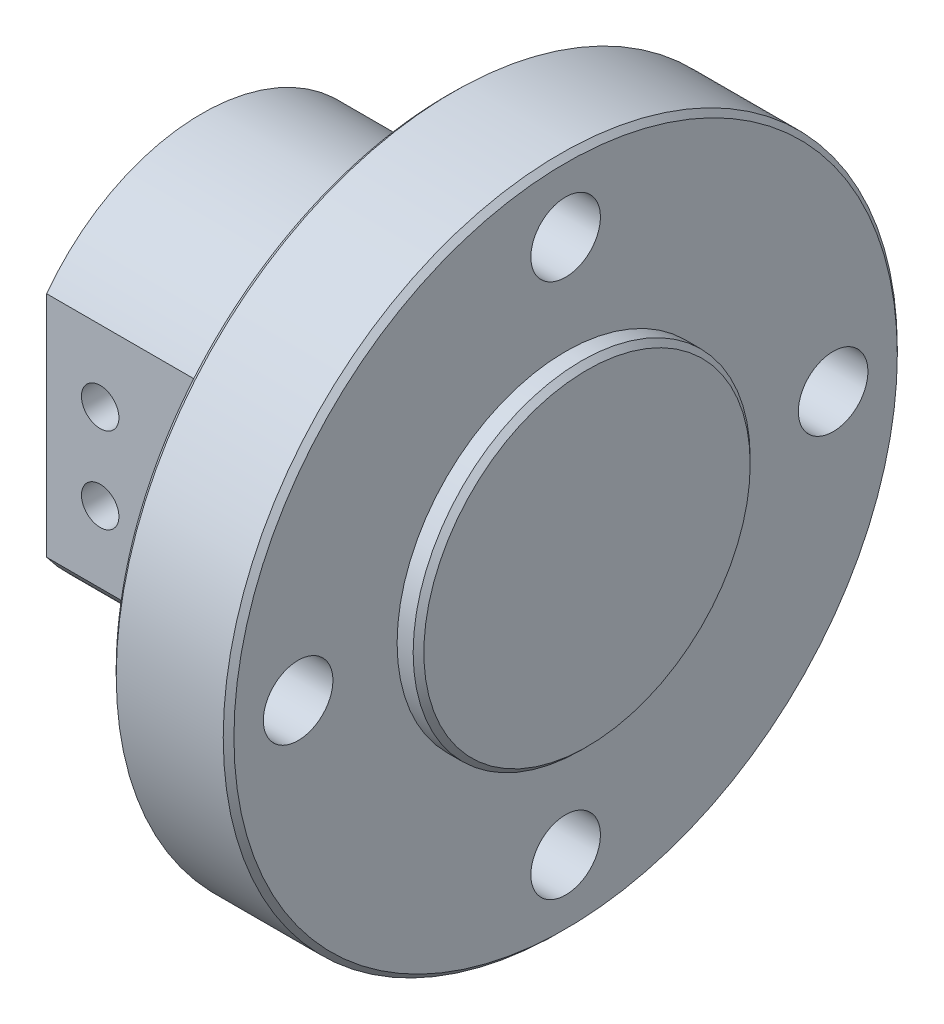
SolidWorks part; units mm, degrees
material "7079 Alloy"
ref_plane "Front Plane" through (0, 0, 0) normal (0, 0, 1) x (1, 0, 0)
ref_plane "Top Plane" through (0, 0, 0) normal (0, 1, 0) x (1, 0, 0)
ref_plane "Right Plane" through (0, 0, 0) normal (1, 0, 0) x (0, 0, -1)
sketch "Sketch1" plane through (0, 0, 0) normal (1, 0, 0) x (0, 0, -1)
  circle A0 centre (0, 0) radius 31.5
  dimension "D1" = 63
extrude "Boss-Extrude1" add sketch "Sketch1" along normal blind 11
sketch "Sketch2" plane through (0, 0, 0) normal (-1, 0, 0) x (0, 0, 1)
  circle A0 centre (0, 0) radius 25 construction
  circle A1 centre (0, 25) radius 3.25
  circle A2 centre (0, -25) radius 3.25
  dimension "D1" = 50
  dimension "D2" = 6.5
extrude "Cut-Extrude1" cut sketch "Sketch2" against normal through all
sketch "Sketch3" plane through (0, 0, 0) normal (-1, 0, 0) x (0, 0, 1)
  circle A0 centre (0, 25) radius 6
  circle A1 centre (0, -25) radius 6
  dimension "D1" = 12
extrude "Cut-Extrude2" cut sketch "Sketch3" against normal blind 5
chamfer "Chamfer1" distance 0.5 angle 45 2 edges at (0, 0, -31.5) (11, 0, -31.5)
sketch "Sketch4" plane through (11, 0, 0) normal (1, 0, 0) x (0, 0, -1)
  circle A0 centre (0, 0) radius 15.75
  dimension "D1" = 31.5
extrude "Boss-Extrude2" add sketch "Sketch4" along normal blind 2
chamfer "Chamfer2" distance 0.5 angle 45 1 edges at (13, 0, -15.75)
sketch "Sketch5" plane through (0, 0, 0) normal (-1, 0, 0) x (0, 0, 1)
  circle A0 centre (0, 0) radius 10.5
  circle A1 centre (0, 0) radius 18
  dimension "D1" = 21
  dimension "D2" = 36
extrude "Boss-Extrude3" add sketch "Sketch5" along normal blind 23
sketch "Sketch6" plane through (-23, 0, 0) normal (-1, 0, 0) x (0, 0, 1)
  line L1 (-8.5, 6.1644) -> (8.5, 6.1644)
  line L2 (-8.5, 6.1644) -> (-8.5, -6.1644)
  line L3 (-8.5, -6.1644) -> (8.5, -6.1644)
  line L4 (8.5, 6.1644) -> (8.5, -6.1644)
  circle A0 centre (0, 0) radius 10.5 construction
  circle A1 centre (0, 0) radius 10.5
  circle M7 centre (0, 0) radius 10.5
  dimension "D1" = 8.5
  dimension "D2" = 12.3288
extrude "Boss-Extrude4" add sketch "Sketch6" against normal up to next contours L4 M7 | L2 M7 region at (-23, 0, -9.3069) region at (-23, 0, 9.3069)
sketch "Sketch7" plane through (-23, 0, 0) normal (-1, 0, 0) x (0, 0, 1)
  line L0 (8.5, 6.1644) -> (8.5, -6.1644) construction
  line L1 (-14.5, 10.6654) -> (14.5, 10.6654)
  line L2 (-14.5, 10.6654) -> (-14.5, -10.6654)
  line L3 (-14.5, -10.6654) -> (14.5, -10.6654)
  line L4 (14.5, 10.6654) -> (14.5, -10.6654)
  circle A1 centre (0, 0) radius 18
  circle A2 centre (0, 0) radius 18
  circle M6 centre (0, 0) radius 18
  dimension "D2" = 6
  dimension "D1" = 0
extrude "Cut-Extrude3" cut sketch "Sketch7" against normal blind 22 contours L4 M6 | L2 M6 region at (-23, 0, -15.9124) region at (-23, 0, 15.9124)
sketch "Sketch8" plane through (0, 0, 14.5) normal (0, 0, 1) x (1, 0, 0)
  line L0 (-23, 10.6654) -> (-23, -10.6654) construction
  line L1 (-18, 4) -> (-6, 4) construction
  line L2 (-18, 4) -> (-18, -4)
  line L3 (-18, -4) -> (-6, -4) construction
  line L4 (-6, 4) -> (-6, -4)
  line L5 (-6, 0) -> (0, 0) construction
  circle A0 centre (-18, 4) radius 1.75
  circle A1 centre (-6, 4) radius 1.75
  circle A2 centre (-6, -4) radius 1.75
  circle A3 centre (-18, -4) radius 1.75
  dimension "D4" = 3.5
  dimension "D1" = 5
  dimension "D2" = 12
  dimension "D3" = 8
extrude "Cut-Extrude4" cut sketch "Sketch8" against normal through all contours A0 | A1 | A2 | A3 region at (-16.7976, -2.7976, 14.5) region at (-19.2024, 5.2024, 14.5) region at (-4.7976, -2.7976, 14.5) region at (-7.2024, 5.2024, 14.5)
pattern_circular "CirPattern1" count 4 over 360 about axis through (11, 0, 0) along (-1, 0, 0) of "Cut-Extrude2", "Cut-Extrude1" reverse direction yes
sketch "Sketch9" plane through (-23, 0, 0) normal (-1, 0, 0) x (0, 0, 1)
  line L0 (-8.5, 6.1644) -> (-8.5, -6.1644) construction
  line L1 (8.5, 6.1644) -> (8.5, -6.1644) construction
  line L2 (-8.5, 6.1644) -> (-8.5, -6.1644)
  line L3 (8.5, 6.1644) -> (8.5, -6.1644)
  line L4 (-8.6, 6.1968) -> (-8.6, -6.1968)
  line L5 (8.6, 6.1968) -> (8.6, -6.1968)
  arc A0 (-8.5, -6.1644) -> (8.5, -6.1644) centre (0, 0) ccw construction
  arc A1 (8.5, 6.1644) -> (-8.5, 6.1644) centre (0, 0) ccw construction
  arc A2 (-8.5, -6.1644) -> (8.5, -6.1644) centre (0, 0) ccw
  arc A3 (8.5, 6.1644) -> (-8.5, 6.1644) centre (0, 0) ccw
  arc A4 (8.6, 6.1968) -> (-8.6, 6.1968) centre (0, 0) ccw
  arc A5 (-8.6, -6.1968) -> (8.6, -6.1968) centre (0, 0) ccw
  dimension "D1" = 0.1
